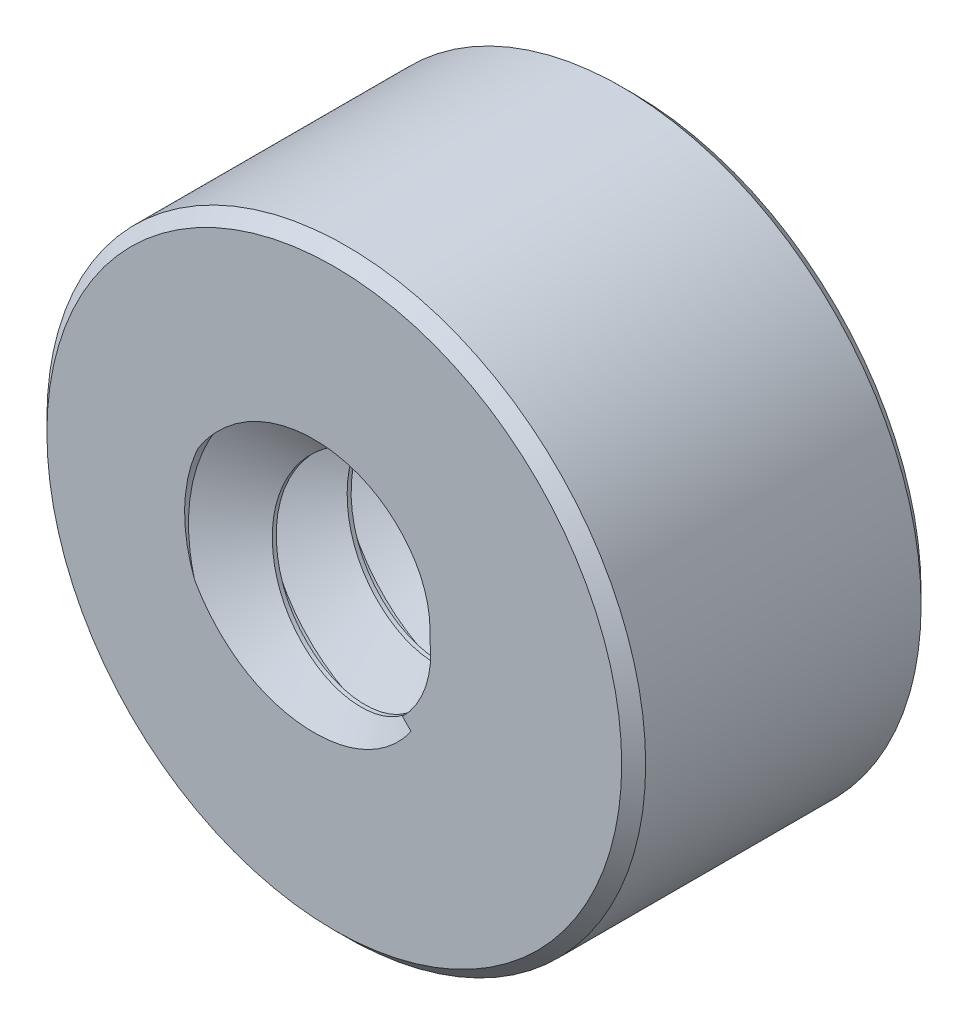
SolidWorks part; units mm, degrees
ref_plane "Front Plane" through (0, 0, 0) normal (0, 0, 1) x (1, 0, 0)
ref_plane "Top Plane" through (0, 0, 0) normal (0, 1, 0) x (1, 0, 0)
ref_plane "Right Plane" through (0, 0, 0) normal (1, 0, 0) x (0, 0, -1)
sketch "Sketch1" plane through (0, 0, 0) normal (0, 0, 1) x (1, 0, 0)
  circle A0 centre (0, 0) radius 6.35
  circle A1 centre (0, 0) radius 2.0447
  dimension "D1" = 12.7
  dimension "D2" = 4.0894
extrude "Boss-Extrude1" add sketch "Sketch1" along normal blind 6.35
sketch "Sketch2" plane through (0, 0, 0) normal (1, 0, 0) x (0, 0, -1)
  line L0 (1.1412, 0) -> (-8.5448, 0) construction
  line L1 (1.1412, 2.0447) -> (0.4886, 3.175)
  line L2 (0.4886, 3.175) -> (0.2902, 3.175)
  line L3 (0.2902, 3.175) -> (-0.3624, 2.0447)
  line L4 (-0.3624, 2.0447) -> (1.1412, 2.0447)
  dimension "D1" = 4.0894
  dimension "D2" = 6.35
  dimension "D3" = 60
  dimension "D4" = 60
  dimension "D5" = 0.1984
sketch "Sketch3" plane through (0, 0, 0) normal (0, 0, -1) x (-1, 0, 0)
  circle A0 centre (0, 0) radius 2.728
  dimension "D1" = 5.4559
curve "Helix/Spiral1" pitch 1.5875 height 7.5406 turns 4.75
sweep "Cut-Sweep1" cut profiles "Sketch2" path "Helix/Spiral1"
chamfer "Chamfer1" distance 0.254 angle 45 2 edges at (6.35, 0, 6.35) (6.35, 0, 0)
